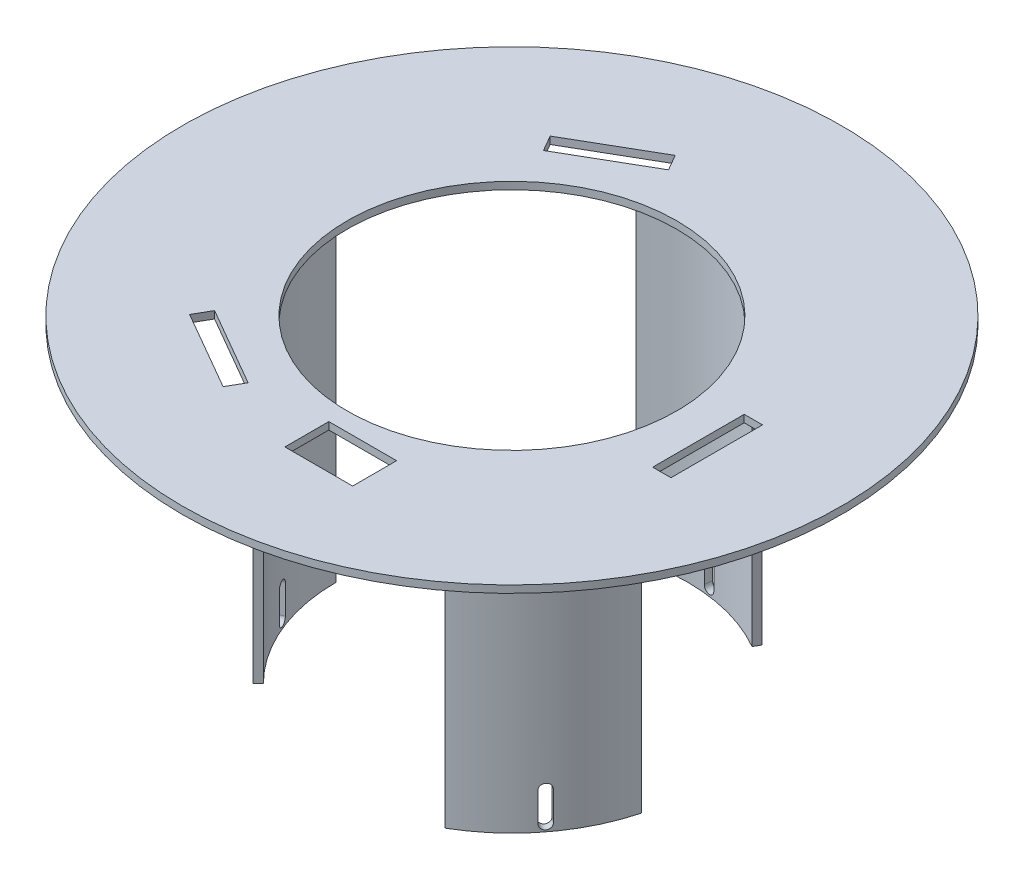
SolidWorks part; units mm, degrees
ref_plane "Front Plane" through (0, 0, 0) normal (0, 0, 1) x (1, 0, 0)
ref_plane "Top Plane" through (0, 0, 0) normal (0, 1, 0) x (1, 0, 0)
ref_plane "Right Plane" through (0, 0, 0) normal (1, 0, 0) x (0, 0, -1)
sketch "Sketch3" plane through (0, 0, 0) normal (0, 1, 0) x (1, 0, 0)
  circle A0 centre (0, 0) radius 90
  dimension "D1" = 180
extrude "Boss-Extrude3" add sketch "Sketch3" along normal blind 2
sketch "Sketch4" plane through (0, 0, 0) normal (0, -1, 0) x (1, 0, 0)
  circle A0 centre (0, 0) radius 45
  dimension "D1" = 90
extrude "Cut-Extrude1" cut sketch "Sketch4" against normal blind 2
sketch "Sketch6" plane through (0, 0, 0) normal (0, -1, 0) x (1, 0, 0)
  line L0 (0, 0) -> (-50, 0)
  line L1 (0, 0) -> (-35.3553, 35.3553)
  arc A0 (-35.3553, 35.3553) -> (-50, 0) centre (0, 0) ccw
  arc A1 (-31.8198, 31.8198) -> (-45, 0) centre (0, 0) ccw
  arc A2 (-32.5269, 32.5269) -> (-46, 0) centre (0, 0) ccw
  arc A3 (-33.9411, 33.9411) -> (-48, 0) centre (0, 0) ccw
  circle M1 centre (0, 0) radius 45
  dimension "D1" = 1
  dimension "D2" = 2
  dimension "D3" = 2
  dimension "D4" = 45
extrude "Boss-Extrude4" add sketch "Sketch6" along normal blind 85 contours A2 M1 region at (-45.5, 0, 0.3548)
extrude "Boss-Extrude5" add sketch "Sketch6<3>" along normal blind 85 contours A0 A3 region at (-49, 0, 0.3883)
sketch "Sketch6<3>" plane through (0, 0, 0) normal (0, -1, 0) x (1, 0, 0) same geometry as "Sketch6"
ref_plane "Plane4" through (-38.4099, 0, 15.9099) normal (0.9239, 0, -0.3827) x (-0.3827, 0, -0.9239)
sketch "Sketch14" plane through (-38.4099, 0, 15.9099) normal (0.9239, 0, -0.3827) x (-0.3827, 0, -0.9239)
  line L0 (0, 0) -> (0, -85) construction
  line L1 (1.5, -75) -> (1.5, -83)
  line L2 (-1.5, -75) -> (-1.5, -83)
  line L4 (19.1342, 0) -> (-19.1342, 0)
  line L5 (19.1342, -85) -> (19.1342, 0)
  line L6 (-19.1342, -85) -> (19.1342, -85)
  line L7 (-19.1342, 0) -> (-19.1342, -85)
  line L8 (19.1342, 0) -> (-19.1342, 0) construction
  line L9 (19.1342, -85) -> (19.1342, 0) construction
  line L10 (-19.1342, -85) -> (19.1342, -85) construction
  line L11 (-19.1342, 0) -> (-19.1342, -85) construction
  arc A0 (-1.5, -83) -> (1.5, -83) centre (0, -83) ccw
  arc A1 (1.5, -75) -> (-1.5, -75) centre (0, -75) ccw
  dimension "D2" = 3
  dimension "D3" = 2
  dimension "D4" = 8
  dimension "D1" = 0
extrude "Cut-Extrude9" cut sketch "Sketch14" against normal blind 10 contours A0 L1 A1 L2
pattern_circular "CirPattern4" count 3 over 360 about axis through (0, 0, 0) along (0, 1, 0) of "Boss-Extrude5", "Cut-Extrude9", "Boss-Extrude4"
sketch "Sketch11" plane through (0, 0, 0) normal (0, -1, 0) x (1, 0, 0)
  line L0 (-6.7476, -52.4795) -> (11.4066, -48.9193)
  line L1 (-6.7476, -52.4795) -> (-4.4382, -64.2552)
  line L2 (11.4066, -48.9193) -> (13.716, -60.695)
  line L3 (-4.4382, -64.2552) -> (13.716, -60.695)
  dimension "D1" = 12
extrude "Cut-Extrude5" cut sketch "Sketch11" against normal mid plane 120
sketch "Sketch15" plane through (0, 2, 0) normal (0, 1, 0) x (1, 0, 0)
  line L1 (55, 8.4328) -> (60, 8.4328)
  line L2 (55, 8.4328) -> (55, -16.5672)
  line L3 (55, -16.5672) -> (60, -16.5672)
  line L4 (60, 8.4328) -> (60, -16.5672)
  circle A0 centre (0, 0) radius 45 construction
  dimension "D1" = 55
  dimension "D2" = 5
  dimension "D3" = 25
extrude "Cut-Extrude10" cut sketch "Sketch15" against normal through all
pattern_circular "CirPattern5" count 3 over 360 about axis through (0, 2, 0) along (0, -1, 0) of "Cut-Extrude10"
sketch "Sketch16" plane through (0, -85, 0) normal (0, -1, 0) x (1, 0, 0)
  circle A0 centre (0, 0) radius 46
extrude "Cut-Extrude11" cut sketch "Sketch16" against normal up to surface (85 mm away) up to face at (-32.2723, 0, 47.7629)
sketch "Sketch17" plane through (0, 2, 0) normal (0, 1, 0) x (1, 0, 0)
  line L0 (13.716, 60.695) -> (-4.4382, 64.2552) construction
  line L1 (13.716, 60.695) -> (-4.4382, 64.2552)
  line L2 (11.4066, 48.9193) -> (13.716, 60.695) construction
  line L3 (11.4066, 48.9193) -> (13.716, 60.695)
  line L4 (-6.7476, 52.4795) -> (11.4066, 48.9193) construction
  line L5 (-6.7476, 52.4795) -> (11.4066, 48.9193)
  line L6 (-4.4382, 64.2552) -> (-6.7476, 52.4795) construction
  line L7 (-4.4382, 64.2552) -> (-6.7476, 52.4795)
extrude "Boss-Extrude6" add sketch "Sketch17" against normal up to surface (2 mm away) up to face at (-32.2723, 0, 47.7629)
sketch "Sketch18" plane through (0, 2, 0) normal (0, 1, 0) x (1, 0, 0)
  line L0 (0, 0) -> (-45, 0) construction
  line L1 (0, -50) -> (18.5, -50)
  line L2 (0, -50) -> (0, -62)
  line L3 (0, -62) -> (18.5, -62)
  line L4 (18.5, -50) -> (18.5, -62)
  line L5 (0, -50) -> (18.5, -62) construction
  line L6 (0, -62) -> (18.5, -50) construction
  circle A0 centre (0, 0) radius 45 construction
  point P0 (9.25, -56)
  dimension "D1" = 50
  dimension "D2" = 12
  dimension "D3" = 18.5
  dimension "D4" = 0
extrude "Cut-Extrude12" cut sketch "Sketch18" against normal up to surface (2 mm away) up to face at (-32.2723, 0, 47.7629)
